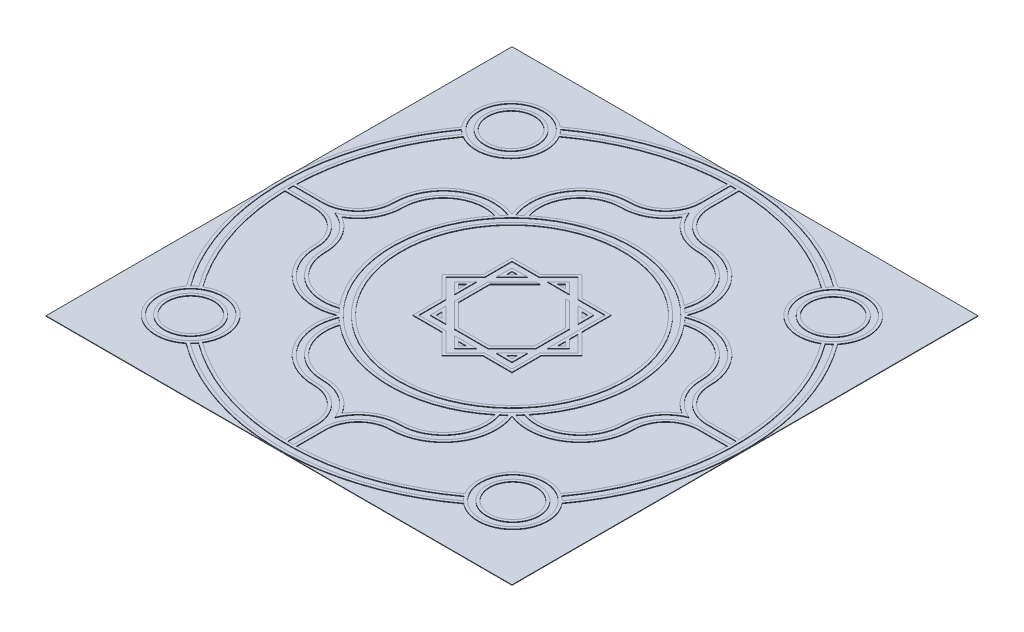
SolidWorks part; units mm, degrees
ref_plane "Front Plane" through (0, 0, 0) normal (0, 0, 1) x (1, 0, 0)
ref_plane "Top Plane" through (0, 0, 0) normal (0, 1, 0) x (1, 0, 0)
ref_plane "Right Plane" through (0, 0, 0) normal (1, 0, 0) x (0, 0, -1)
sketch "Sketch1" plane through (0, 0, 0) normal (0, 1, 0) x (1, 0, 0)
  line L1 (-101.6, -101.6) -> (101.6, -101.6)
  line L2 (-101.6, -101.6) -> (-101.6, 101.6)
  line L3 (-101.6, 101.6) -> (101.6, 101.6)
  line L4 (101.6, -101.6) -> (101.6, 101.6)
  line L5 (-101.6, -101.6) -> (101.6, 101.6) construction
  line L6 (-101.6, 101.6) -> (101.6, -101.6) construction
  point P0 (0, 0)
  dimension "D1" = 203.2
  dimension "D2" = 203.2
extrude "Boss-Extrude1" add sketch "Sketch1" along normal blind 0.2032 contours L1 L4 L3 L2
sketch "Sketch2" plane through (0, 0.2032, 0) normal (0, 1, 0) x (1, 0, 0)
  line L0 (-101.6, 101.6) -> (101.6, 101.6) construction
  line L1 (0, 26.9408) -> (26.9408, 0) construction
  line L2 (-19.05, -19.05) -> (19.05, -19.05) construction
  line L3 (-19.05, -19.05) -> (-19.05, 19.05) construction
  line L4 (-19.05, 19.05) -> (19.05, 19.05) construction
  line L5 (19.05, -19.05) -> (19.05, 19.05) construction
  line L6 (-19.05, -19.05) -> (19.05, 19.05) construction
  line L7 (-19.05, 19.05) -> (19.05, -19.05) construction
  line L8 (26.9408, 0) -> (0, -26.9408) construction
  line L9 (0, -26.9408) -> (-26.9408, 0) construction
  line L10 (-26.9408, 0) -> (0, 26.9408) construction
  line L11 (0, 26.9408) -> (0, -26.9408) construction
  line L12 (-20.32, 20.32) -> (20.32, 20.32)
  line L13 (20.32, -20.32) -> (20.32, 20.32)
  line L14 (-20.32, -20.32) -> (20.32, -20.32)
  line L15 (-20.32, -20.32) -> (-20.32, 20.32)
  line L16 (-28.7368, 0) -> (0, 28.7368)
  line L17 (0, 28.7368) -> (28.7368, 0)
  line L18 (28.7368, 0) -> (0, -28.7368)
  line L19 (0, -28.7368) -> (-28.7368, 0)
  line L20 (-17.78, 17.78) -> (17.78, 17.78)
  line L21 (17.78, -17.78) -> (17.78, 17.78)
  line L22 (-17.78, -17.78) -> (17.78, -17.78)
  line L23 (-17.78, -17.78) -> (-17.78, 17.78)
  line L24 (-25.1447, 0) -> (0, 25.1447)
  line L25 (0, 25.1447) -> (25.1447, 0)
  line L26 (25.1447, 0) -> (0, -25.1447)
  line L27 (0, -25.1447) -> (-25.1447, 0)
  line L28 (-30.5329, 0) -> (0, 30.5329)
  line L29 (0, 30.5329) -> (30.5329, 0)
  line L30 (30.5329, 0) -> (0, -30.5329)
  line L31 (0, -30.5329) -> (-30.5329, 0)
  line L32 (-21.59, -21.59) -> (-21.59, 21.59)
  line L33 (-21.59, 21.59) -> (21.59, 21.59)
  line L34 (21.59, -21.59) -> (21.59, 21.59)
  line L35 (-21.59, -21.59) -> (21.59, -21.59)
  line L36 (-16.51, -16.51) -> (-16.51, 16.51)
  line L37 (-16.51, 16.51) -> (16.51, 16.51)
  line L38 (16.51, -16.51) -> (16.51, 16.51)
  line L39 (-16.51, -16.51) -> (16.51, -16.51)
  line L40 (-23.3487, 0) -> (0, 23.3487)
  line L41 (0, 23.3487) -> (23.3487, 0)
  line L42 (23.3487, 0) -> (0, -23.3487)
  line L43 (0, -23.3487) -> (-23.3487, 0)
  line L44 (0, 96.52) -> (0, 83.82) construction
  line L45 (-35.921, -35.921) -> (35.921, -35.921) construction
  line L46 (-35.921, -35.921) -> (-35.921, 35.921) construction
  line L47 (-35.921, 35.921) -> (35.921, 35.921) construction
  line L48 (35.921, -35.921) -> (35.921, 35.921) construction
  line L49 (-35.921, -35.921) -> (35.921, 35.921) construction
  line L50 (-35.921, 35.921) -> (35.921, -35.921) construction
  line L51 (-1.27, 96.52) -> (-1.27, 83.82)
  line L52 (1.27, 96.5116) -> (1.27, 83.82)
  line L53 (2.54, 96.4866) -> (2.54, 83.82)
  line L54 (-2.54, 96.4866) -> (-2.54, 83.82)
  line L55 (-2.54, 96.52) -> (-2.54, 83.82) construction
  line L56 (1.27, 96.52) -> (1.27, 83.82) construction
  line L57 (2.54, 96.52) -> (2.54, 83.82) construction
  line L58 (96.52, 1.27) -> (83.82, 1.27)
  line L59 (96.5116, -1.27) -> (83.82, -1.27)
  line L60 (96.4866, -2.54) -> (83.82, -2.54)
  line L61 (96.4866, 2.54) -> (83.82, 2.54)
  line L62 (96.52, 0) -> (83.82, 0) construction
  line L63 (35.921, 35.921) -> (35.921, -35.921) construction
  line L64 (1.27, -96.52) -> (1.27, -83.82)
  line L65 (-1.27, -96.5116) -> (-1.27, -83.82)
  line L66 (-2.54, -96.4866) -> (-2.54, -83.82)
  line L67 (2.54, -96.4866) -> (2.54, -83.82)
  line L68 (0, -96.52) -> (0, -83.82) construction
  line L69 (35.921, -35.921) -> (-35.921, -35.921) construction
  line L70 (-96.52, -1.27) -> (-83.82, -1.27)
  line L71 (-96.5116, 1.27) -> (-83.82, 1.27)
  line L72 (-96.4866, 2.54) -> (-83.82, 2.54)
  line L73 (-96.4866, -2.54) -> (-83.82, -2.54)
  line L74 (-96.52, 0) -> (-83.82, 0) construction
  line L75 (-35.921, -35.921) -> (-35.921, 35.921) construction
  circle A0 centre (0, 0) radius 101.6
  circle A5 centre (0, 0) radius 100.33
  circle A6 centre (0, 0) radius 99.06 construction
  circle A7 centre (0, 0) radius 97.79
  circle A8 centre (0, 0) radius 96.52
  circle A9 centre (-70.2414, 69.85) radius 12.7 construction
  circle A10 centre (70.2414, 69.85) radius 12.7 construction
  circle A11 centre (70.2414, -69.85) radius 12.7 construction
  circle A12 centre (-70.2414, -69.85) radius 12.7 construction
  circle A13 centre (-70.2414, 69.85) radius 13.97
  circle A14 centre (70.2414, 69.85) radius 13.97
  circle A15 centre (70.2414, -69.85) radius 13.97
  circle A16 centre (-70.2414, -69.85) radius 13.97
  circle A17 centre (-70.2414, 69.85) radius 11.43
  circle A18 centre (70.2414, 69.85) radius 11.43
  circle A19 centre (70.2414, -69.85) radius 11.43
  circle A20 centre (-70.2414, -69.85) radius 11.43
  circle A21 centre (0, 0) radius 50.8 construction
  circle A22 centre (0, 0) radius 52.07
  circle A23 centre (0, 0) radius 49.53
  circle A24 centre (0, 0) radius 48.26
  circle A25 centre (0, 0) radius 53.34
  arc A26 (-35.921, 39.4314) -> (-16.764, 67.056) centre (-16.764, 46.6012) cw construction
  arc A27 (-16.764, 67.056) -> (0, 83.82) centre (-16.764, 83.82) ccw construction
  arc A28 (0, 83.82) -> (16.764, 67.056) centre (16.764, 83.82) ccw construction
  arc A29 (16.764, 67.056) -> (35.921, 39.4314) centre (16.764, 46.6012) cw construction
  arc A30 (-34.7316, 39.8766) -> (-16.764, 65.786) centre (-16.764, 46.6012) cw construction
  arc A31 (16.764, 65.786) -> (34.8981, 40.3395) centre (16.764, 46.6012) cw
  arc A32 (-34.8981, 40.3395) -> (-16.764, 65.786) centre (-16.764, 46.6012) cw
  arc A33 (-16.764, 65.786) -> (0, 77.1722) centre (-16.764, 83.82) ccw
  arc A34 (1.27, 83.82) -> (16.764, 68.326) centre (16.764, 83.82) ccw
  arc A35 (16.764, 68.326) -> (36.9206, 38.4971) centre (16.764, 46.6012) cw
  arc A36 (-36.9206, 38.4971) -> (-16.764, 68.326) centre (-16.764, 46.6012) cw
  arc A37 (-16.764, 68.326) -> (-1.27, 83.82) centre (-16.764, 83.82) ccw
  arc A38 (0, 77.1722) -> (16.764, 65.786) centre (16.764, 83.82) ccw
  arc A39 (-1.27, 83.82) -> (16.764, 65.786) centre (16.764, 83.82) ccw construction
  arc A40 (16.764, 65.786) -> (34.7316, 39.8766) centre (16.764, 46.6012) cw construction
  arc A41 (-16.764, 65.786) -> (1.27, 83.82) centre (-16.764, 83.82) ccw construction
  arc A42 (-37.1104, 38.9862) -> (-16.764, 68.326) centre (-16.764, 46.6012) cw construction
  arc A43 (16.764, 68.326) -> (37.1104, 38.9862) centre (16.764, 46.6012) cw construction
  arc A44 (-37.8967, 37.5366) -> (-16.764, 69.596) centre (-16.764, 46.6012) cw
  arc A45 (-16.764, 69.596) -> (-2.54, 83.82) centre (-16.764, 83.82) ccw
  arc A46 (2.54, 83.82) -> (16.764, 69.596) centre (16.764, 83.82) ccw
  arc A47 (16.764, 69.596) -> (37.8967, 37.5366) centre (16.764, 46.6012) cw
  arc A48 (-33.8519, 41.2214) -> (-16.764, 64.516) centre (-16.764, 46.6012) cw
  arc A49 (-16.764, 64.516) -> (0, 74.2485) centre (-16.764, 83.82) ccw
  arc A50 (0, 74.2485) -> (16.764, 64.516) centre (16.764, 83.82) ccw
  arc A51 (16.764, 64.516) -> (33.8519, 41.2214) centre (16.764, 46.6012) cw
  arc A52 (-33.6977, 40.754) -> (-16.764, 64.516) centre (-16.764, 46.6012) cw construction
  arc A53 (16.764, 64.516) -> (33.6977, 40.754) centre (16.764, 46.6012) cw construction
  arc A54 (16.764, 69.596) -> (38.0989, 38.0233) centre (16.764, 46.6012) cw construction
  arc A55 (-38.0989, 38.0233) -> (-16.764, 69.596) centre (-16.764, 46.6012) cw construction
  arc A56 (65.786, -16.764) -> (40.3395, -34.8981) centre (46.6012, -16.764) cw
  arc A57 (40.3395, 34.8981) -> (65.786, 16.764) centre (46.6012, 16.764) cw
  arc A58 (65.786, 16.764) -> (77.1722, 0) centre (83.82, 16.764) ccw
  arc A59 (83.82, -1.27) -> (68.326, -16.764) centre (83.82, -16.764) ccw
  arc A60 (68.326, -16.764) -> (38.4971, -36.9206) centre (46.6012, -16.764) cw
  arc A61 (38.4971, 36.9206) -> (68.326, 16.764) centre (46.6012, 16.764) cw
  arc A62 (68.326, 16.764) -> (83.82, 1.27) centre (83.82, 16.764) ccw
  arc A63 (77.1722, 0) -> (65.786, -16.764) centre (83.82, -16.764) ccw
  arc A64 (37.5366, 37.8967) -> (69.596, 16.764) centre (46.6012, 16.764) cw
  arc A65 (69.596, 16.764) -> (83.82, 2.54) centre (83.82, 16.764) ccw
  arc A66 (83.82, -2.54) -> (69.596, -16.764) centre (83.82, -16.764) ccw
  arc A67 (69.596, -16.764) -> (37.5366, -37.8967) centre (46.6012, -16.764) cw
  arc A68 (41.2214, 33.8519) -> (64.516, 16.764) centre (46.6012, 16.764) cw
  arc A69 (64.516, 16.764) -> (74.2485, 0) centre (83.82, 16.764) ccw
  arc A70 (74.2485, 0) -> (64.516, -16.764) centre (83.82, -16.764) ccw
  arc A71 (64.516, -16.764) -> (41.2214, -33.8519) centre (46.6012, -16.764) cw
  arc A72 (39.4314, 35.921) -> (67.056, 16.764) centre (46.6012, 16.764) cw construction
  arc A73 (67.056, 16.764) -> (83.82, 0) centre (83.82, 16.764) ccw construction
  arc A74 (83.82, 0) -> (67.056, -16.764) centre (83.82, -16.764) ccw construction
  arc A75 (67.056, -16.764) -> (39.4314, -35.921) centre (46.6012, -16.764) cw construction
  circle A76 centre (0, 0) radius 53.34
  circle A77 centre (0, 0) radius 96.52
  arc A78 (-16.764, -65.786) -> (-34.8981, -40.3395) centre (-16.764, -46.6012) cw
  arc A79 (34.8981, -40.3395) -> (16.764, -65.786) centre (16.764, -46.6012) cw
  arc A80 (16.764, -65.786) -> (0, -77.1722) centre (16.764, -83.82) ccw
  arc A81 (-1.27, -83.82) -> (-16.764, -68.326) centre (-16.764, -83.82) ccw
  arc A82 (-16.764, -68.326) -> (-36.9206, -38.4971) centre (-16.764, -46.6012) cw
  arc A83 (36.9206, -38.4971) -> (16.764, -68.326) centre (16.764, -46.6012) cw
  arc A84 (16.764, -68.326) -> (1.27, -83.82) centre (16.764, -83.82) ccw
  arc A85 (0, -77.1722) -> (-16.764, -65.786) centre (-16.764, -83.82) ccw
  arc A86 (37.8967, -37.5366) -> (16.764, -69.596) centre (16.764, -46.6012) cw
  arc A87 (16.764, -69.596) -> (2.54, -83.82) centre (16.764, -83.82) ccw
  arc A88 (-2.54, -83.82) -> (-16.764, -69.596) centre (-16.764, -83.82) ccw
  arc A89 (-16.764, -69.596) -> (-37.8967, -37.5366) centre (-16.764, -46.6012) cw
  arc A90 (33.8519, -41.2214) -> (16.764, -64.516) centre (16.764, -46.6012) cw
  arc A91 (16.764, -64.516) -> (0, -74.2485) centre (16.764, -83.82) ccw
  arc A92 (0, -74.2485) -> (-16.764, -64.516) centre (-16.764, -83.82) ccw
  arc A93 (-16.764, -64.516) -> (-33.8519, -41.2214) centre (-16.764, -46.6012) cw
  arc A94 (35.921, -39.4314) -> (16.764, -67.056) centre (16.764, -46.6012) cw construction
  arc A95 (16.764, -67.056) -> (0, -83.82) centre (16.764, -83.82) ccw construction
  arc A96 (0, -83.82) -> (-16.764, -67.056) centre (-16.764, -83.82) ccw construction
  arc A97 (-16.764, -67.056) -> (-35.921, -39.4314) centre (-16.764, -46.6012) cw construction
  circle A98 centre (0, 0) radius 53.34
  circle A99 centre (0, 0) radius 96.52
  arc A100 (-65.786, 16.764) -> (-40.3395, 34.8981) centre (-46.6012, 16.764) cw
  arc A101 (-40.3395, -34.8981) -> (-65.786, -16.764) centre (-46.6012, -16.764) cw
  arc A102 (-65.786, -16.764) -> (-77.1722, 0) centre (-83.82, -16.764) ccw
  arc A103 (-83.82, 1.27) -> (-68.326, 16.764) centre (-83.82, 16.764) ccw
  arc A104 (-68.326, 16.764) -> (-38.4971, 36.9206) centre (-46.6012, 16.764) cw
  arc A105 (-38.4971, -36.9206) -> (-68.326, -16.764) centre (-46.6012, -16.764) cw
  arc A106 (-68.326, -16.764) -> (-83.82, -1.27) centre (-83.82, -16.764) ccw
  arc A107 (-77.1722, 0) -> (-65.786, 16.764) centre (-83.82, 16.764) ccw
  arc A108 (-37.5366, -37.8967) -> (-69.596, -16.764) centre (-46.6012, -16.764) cw
  arc A109 (-69.596, -16.764) -> (-83.82, -2.54) centre (-83.82, -16.764) ccw
  arc A110 (-83.82, 2.54) -> (-69.596, 16.764) centre (-83.82, 16.764) ccw
  arc A111 (-69.596, 16.764) -> (-37.5366, 37.8967) centre (-46.6012, 16.764) cw
  arc A112 (-41.2214, -33.8519) -> (-64.516, -16.764) centre (-46.6012, -16.764) cw
  arc A113 (-64.516, -16.764) -> (-74.2485, 0) centre (-83.82, -16.764) ccw
  arc A114 (-74.2485, 0) -> (-64.516, 16.764) centre (-83.82, 16.764) ccw
  arc A115 (-64.516, 16.764) -> (-41.2214, 33.8519) centre (-46.6012, 16.764) cw
  arc A116 (-39.4314, -35.921) -> (-67.056, -16.764) centre (-46.6012, -16.764) cw construction
  arc A117 (-67.056, -16.764) -> (-83.82, 0) centre (-83.82, -16.764) ccw construction
  arc A118 (-83.82, 0) -> (-67.056, 16.764) centre (-83.82, 16.764) ccw construction
  arc A119 (-67.056, 16.764) -> (-39.4314, 35.921) centre (-46.6012, 16.764) cw construction
  circle A120 centre (0, 0) radius 53.34
  circle A121 centre (0, 0) radius 96.52
  circle A122 centre (-70.2414, 69.85) radius 15.24
  circle A123 centre (70.2414, 69.85) radius 15.24
  circle A124 centre (70.2414, -69.85) radius 15.24
  circle A125 centre (-70.2414, -69.85) radius 15.24
  circle A126 centre (-70.2414, -69.85) radius 10.16
  circle A127 centre (70.2414, -69.85) radius 10.16
  circle A128 centre (-70.2414, 69.85) radius 10.16
  circle A129 centre (70.2414, 69.85) radius 10.16
  point P54 (0, 0)
  point P334 (0, 0)
  dimension "D1" = 1.27
  dimension "D3" = 1.27
  dimension "D2" = 1.27
  dimension "D5" = 25.4
  dimension "D9" = 101.6
  dimension "D20" = 16.764
  dimension "D6" = 139.7
  dimension "D14" = 38.1
  dimension "D19" = 12.7
  dimension "D4" = 1.27
  dimension "D7" = 1.27
  dimension "D8" = 1.27
  dimension "D10" = 1.27
  dimension "D11" = 1.27
  dimension "D12" = 1.27
  dimension "D13" = 1.27
  dimension "D15" = 1.27
  dimension "D16" = 1.27
  dimension "D17" = 1.27
  dimension "D18" = 1.27
  dimension "D21" = 1.27
  dimension "D22" = 1.27
  dimension "D23" = 1.27
  dimension "D24" = 1.27
  dimension "D26" = 1.27
  dimension "D27" = 1.27
  dimension "D25" = 4
extrude "Boss-Extrude2" add sketch "Sketch2" along normal blind 0.254 contours A128 A0 A17 | A0 A122 A13 | A128 A5 A17 A0 | A128 A7 A17 A5 | A128 A8 A17 A7 | A121 A122 A7 A13 | A5 A122 A0 A13 | A7 A122 A5 A13 | A8 A122 A121 A13 | A128 A8 A17 | A128 A0 A17 A5 | A128 A5 A17 A7 | A128 A7 A17 A8 | A7 A122 A8 A13 | A5 A122 A7 A13 | A0 A122 A5 A13 | A125 A5 A122 A0 | A125 A8 A121 A122 A7 | A121 A125 A7 A16 | A7 A125 A5 A16 | A5 A125 A0 A16 | A8 A125 A121 A16 | A126 A8 A20 | A126 A8 A20 A7 | A126 A7 A20 A5 | A126 A5 A20 A0 | A126 A0 A20 | A0 A125 A16 | A126 A7 A20 A8 | A126 A5 A20 A7 | A126 A0 A20 A5 | A7 A125 A8 A16 | A5 A125 A7 A16 | A0 A125 A5 A16 | A125 A0 A124 A5 | A125 A7 A124 A8 A121 | A121 A124 A7 A15 | A7 A124 A5 A15 | A5 A124 A0 A15 | A127 A5 A19 A0 | A127 A7 A19 A5 | A127 A8 A19 A7 | A0 A124 A15 | A127 A0 A19 | A8 A124 A121 A15 | A127 A8 A19 | A127 A7 A19 A8 | A127 A5 A19 A7 | A127 A0 A19 A5 | A0 A124 A5 A15 | A5 A124 A7 A15 | A7 A124 A8 A15 | A124 A0 A123 A5 | A124 A7 A123 A8 A121 | A129 A5 A18 A0 | A129 A7 A18 A5 | A129 A8 A18 A7 | A121 A123 A7 A14 | A7 A123 A5 A14 | A5 A123 A0 A14 | A8 A123 A121 A14 | A0 A123 A14 | A129 A8 A18 | A129 A0 A18 | A129 A0 A18 A5 | A129 A5 A18 A7 | A129 A7 A18 A8 | A0 A123 A5 A14 | A5 A123 A7 A14 | A7 A123 A8 A14 | A123 A0 A122 A5 | A123 A7 A122 A8 A121 region at (-1.9282, 0.2032, -97.6763) region at (-55.877, 0.2032, -73.859) region at (-58.0592, 0.2032, -77.8973) region at (58.0592, 0.2032, -77.8973) region at (57.5215, 0.2032, -77.1002) region at (-59.2239, 0.2032, -79.4092) region at (59.2239, 0.2032, -79.4092) region at (79.2388, 0.2032, -56.1311) region at (78.2205, 0.2032, -57.6229) region at (-59.4095, 0.2032, -72.6589) region at (-61.0816, 0.2032, -75.5493) region at (-78.2205, 0.2032, -57.6229) region at (-92.4926, 0.2032, -31.4277) region at (-59.2208, 0.2032, -82.0875) region at (-60.5658, 0.2032, -80.7834) region at (61.0816, 0.2032, -75.5493) region at (60.6041, 0.2032, -74.8132) region at (60.5658, 0.2032, -80.7834) region at (79.7389, 0.2032, -58.7792) region at (-62.2448, 0.2032, -77.0641) region at (-79.7389, 0.2032, -58.7792) region at (-61.2705, 0.2032, -81.4886) region at (62.2448, 0.2032, -77.0641) region at (75.8894, 0.2032, -60.6584) region at (76.5837, 0.2032, -83.3181) region at (82.4101, 0.2032, -58.7675) region at (81.1206, 0.2032, -60.1134) region at (-75.8894, 0.2032, -60.6584) region at (-63.6424, 0.2032, -78.3838) region at (-78.2205, 0.2032, 57.6229) region at (-79.7389, 0.2032, 58.7792) region at (-81.1206, 0.2032, -60.1134) region at (-101.549, 0.2032, 0) region at (63.6424, 0.2032, -78.3838) region at (77.4107, 0.2032, -61.8131) region at (79.7389, 0.2032, 58.7792) region at (78.2205, 0.2032, 57.6229) region at (-77.4107, 0.2032, -61.8131) region at (-64.3284, 0.2032, -78.9705) region at (-62.8828, 0.2032, 56.8785) region at (-81.1206, 0.2032, 60.1134) region at (-81.8297, 0.2032, 60.8142) region at (75.3837, 0.2032, -79.7714) region at (78.7383, 0.2032, -63.2033) region at (81.1206, 0.2032, 60.1134) region at (77.4204, 0.2032, 57.0898) region at (-78.7383, 0.2032, -63.2033) region at (-75.8894, 0.2032, 60.6584) region at (-77.4107, 0.2032, 61.8131) region at (-59.2208, 0.2032, 82.0875) region at (-60.5658, 0.2032, 80.7834) region at (77.4107, 0.2032, 61.8131) region at (75.8894, 0.2032, 60.6584) region at (84.2353, 0.2032, 64.7721) region at (56.5653, 0.2032, 78.929) region at (58.0592, 0.2032, 77.8973) region at (-64.5414, 0.2032, 60.2204) region at (-78.7383, 0.2032, 63.2033) region at (-58.0592, 0.2032, 77.8973) region at (-79.3288, 0.2032, 63.8861)
extrude "Boss-Extrude3" add sketch "Sketch2<7>" along normal blind 0.254 contours A44 A111 A25 A36 A37 L51 A8 L54 A45 | A50 A51 A25 A31 A38 A33 A32 A48 A49 | A25 A64 A47 A46 L53 A8 L52 A34 A35 | A65 A64 A47 A25 A61 A62 L58 A8 L61 | A25 A98 A76 A22 | A64 A25 A47 | A70 A71 A25 A56 A63 A58 A57 A68 A69 | A76 A86 A67 A66 L60 A8 L59 A59 A60 | A86 A25 A67 | A87 A86 A67 A76 A83 A84 L64 A8 L67 | A92 A93 A76 A78 A85 A80 A79 A25 A90 A91 | A98 A108 A89 A88 L66 A8 L65 A81 A82 | A108 A76 A89 | A109 A108 A89 A98 A105 A106 L70 A8 L73 | A114 A115 A98 A100 A107 A102 A101 A25 A112 A113 | A111 A110 L72 A8 L71 A103 A104 A25 A44 | A111 A44 A98 | A23 A24 | L20 L41 L37 L25 | L37 L41 L38 L25 | L40 L41 L33 L25 L24 | L33 L41 L12 L25 | L12 L40 L33 L24 | L37 L40 L20 L24 | L36 L40 L37 L24 | L28 L37 L16 L20 | L33 L28 L12 L16 | L28 L33 L16 L17 L29 | L33 L17 L12 L29 | L29 L34 L33 L12 L13 | L33 L32 L28 L15 L12 | L36 L37 L28 L20 L23 | L16 L36 L28 L23 | L17 L37 L29 L20 | L38 L29 L21 L20 L37 | L38 L17 L21 L29 | L38 L41 L21 L25 | L23 L40 L36 L24 | L17 L34 L29 L13 | L25 L34 L17 L13 | L17 L38 L29 L37 | L32 L16 L15 L28 | L31 L32 L19 L16 L28 | L32 L40 L15 L24 | L32 L43 L40 L24 L27 | L43 L15 L40 L32 | L43 L36 L40 L23 | L15 L43 L32 L27 | L32 L31 L15 L19 | L36 L43 L23 L27 | L31 L36 L19 L23 | L32 L35 L31 L14 L15 | L39 L36 L31 L23 L22 | L31 L39 L19 L36 | L39 L31 L22 L19 | L39 L43 L36 L27 | L22 L43 L39 L27 | L31 L35 L19 L14 | L35 L43 L14 L27 | L42 L43 L35 L27 L26 | L35 L31 L30 L18 L19 | L18 L35 L30 L14 | L43 L35 L42 L14 | L14 L42 L35 L26 | L30 L35 L34 L13 L14 | L39 L42 L22 L26 | L43 L22 L42 L39 | L39 L18 L22 L30 | L39 L30 L22 L21 L38 | L38 L30 L21 L18 | L18 L39 L30 L38 | L38 L42 L39 L26 | L21 L42 L38 L26 | L30 L34 L18 L13 | L34 L30 L29 L17 L18 | L13 L41 L34 L25 | L41 L42 L34 L26 L25 | L42 L34 L41 L13 | L34 L42 L13 L26 | L42 L21 L41 L38 | L41 L33 L40 L12 | L37 L28 L36 L16 region at (-20.4989, 0.2032, -15.2664) region at (-8.6798, 0.2032, -20.955) region at (-20.955, 0.2032, -8.6798) region at (-13.4381, 0.2032, -17.1953) region at (-12.4898, 0.2032, -17.145) region at (-4.33, 0.2032, -25.92) region at (-21.79, 0.2032, -8.0448) region at (-17.145, 0.2032, -12.4898) region at (-3.2917, 0.2032, -20.955) region at (-14.7777, 0.2032, -14.7777) region at (-20.955, 0.2032, -3.2917) region at (0, 0.2032, -20.8988) region at (-7.1017, 0.2032, -17.145) region at (-1.7212, 0.2032, -23.3112) region at (15.2664, 0.2032, -21.4111) region at (8.6798, 0.2032, -20.955) region at (-20.8988, 0.2032, 0) region at (-21.6695, 0.2032, -2.6567) region at (-17.145, 0.2032, -7.1017) region at (-20.955, 0.2032, 8.6798) region at (-21.0815, 0.2032, 9.7043) region at (3.2917, 0.2032, -20.955) region at (-12.108, 0.2032, -12.108) region at (-20.955, 0.2032, 3.2917) region at (-17.1233, 0.2032, 0) region at (7.1017, 0.2032, -17.145) region at (12.4898, 0.2032, -17.145) region at (15.2664, 0.2032, -17.7089) region at (20.955, 0.2032, -8.6798) region at (25.92, 0.2032, -4.33) region at (-17.145, 0.2032, 7.1017) region at (-17.1953, 0.2032, 13.4381) region at (-17.145, 0.2032, 12.4898) region at (-8.0448, 0.2032, 21.79) region at (-8.6798, 0.2032, 20.955) region at (12.108, 0.2032, -12.108) region at (14.7777, 0.2032, -14.7777) region at (20.955, 0.2032, -5.9858) region at (-12.108, 0.2032, 12.108) region at (-14.7777, 0.2032, 14.7777) region at (17.1233, 0.2032, 0) region at (17.145, 0.2032, -7.1017) region at (17.145, 0.2032, -12.4898) region at (21.4111, 0.2032, 15.2664) region at (20.955, 0.2032, 8.6798) region at (20.955, 0.2032, -3.2917) region at (23.3112, 0.2032, -1.7212) region at (-7.1017, 0.2032, 17.145) region at (0, 0.2032, 17.1233) region at (-12.4898, 0.2032, 17.145) region at (8.6798, 0.2032, 20.955) region at (-2.6567, 0.2032, 21.6695) region at (-3.2917, 0.2032, 20.955) region at (17.145, 0.2032, 7.1017) region at (12.108, 0.2032, 12.108) region at (20.8988, 0.2032, 0) region at (7.1017, 0.2032, 17.145) region at (0, 0.2032, 20.8988) region at (17.145, 0.2032, 12.4898) region at (17.7089, 0.2032, 15.2664)
sketch "Sketch2<7>" plane through (0, 0.2032, 0) normal (0, 1, 0) x (1, 0, 0) same geometry as "Sketch2"
